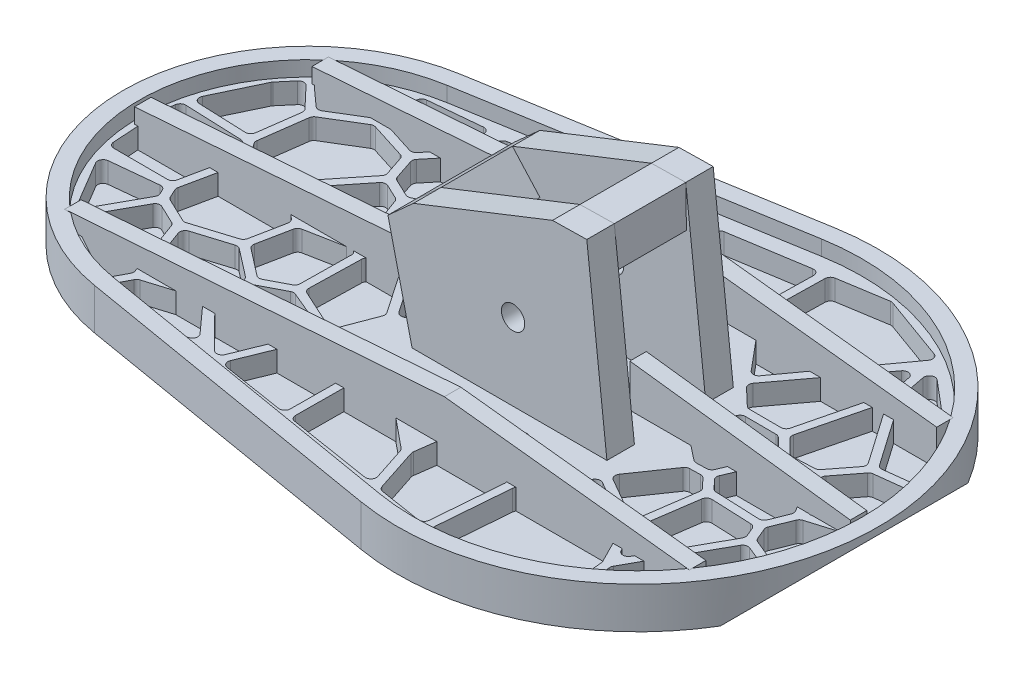
SolidWorks part; units mm, degrees
ref_plane "Front Plane" through (0, 0, 0) normal (0, 0, 1) x (1, 0, 0)
ref_plane "Top Plane" through (0, 0, 0) normal (0, 1, 0) x (1, 0, 0)
ref_plane "Right Plane" through (0, 0, 0) normal (1, 0, 0) x (0, 0, -1)
ref_plane "Plane1" through (0, 34.8481, 0) normal (0, 1, 0) x (1, 0, 0)
sketch "Sketch1" plane through (0, 34.8481, 0) normal (0, 1, 0) x (1, 0, 0)
  line L0 (258.2306, -326.3776) -> (304.8973, -318.4895)
  line L1 (304.8973, -387.5105) -> (258.2306, -379.6224)
  arc A0 (304.8973, -318.4895) -> (304.8973, -387.5105) centre (310.7306, -353) cw
  arc A1 (258.2306, -379.6224) -> (258.2306, -326.3776) centre (262.7306, -353) cw
extrude "Boss-Extrude1" add sketch "Sketch1" along normal blind 0.8
sketch "Sketch2" plane through (0, 34.8481, 0) normal (0, 1, 0) x (1, 0, 0)
  line L0 (258.2306, -326.3776) -> (304.8973, -318.4895)
  line L1 (304.8973, -387.5105) -> (258.2306, -379.6224)
  line L2 (258.6306, -328.7441) -> (305.2973, -320.856)
  line L3 (305.2973, -385.144) -> (258.6306, -377.2559)
  arc A0 (304.8973, -318.4895) -> (304.8973, -387.5105) centre (310.7306, -353) cw
  arc A1 (258.2306, -379.6224) -> (258.2306, -326.3776) centre (262.7306, -353) cw
  arc A2 (305.2973, -320.856) -> (305.2973, -385.144) centre (310.7306, -353) cw
  arc A3 (258.6306, -377.2559) -> (258.6306, -328.7441) centre (262.7306, -353) cw
extrude "Boss-Extrude2" add sketch "Sketch2" along normal blind 6
ref_plane "Plane2" through (0, 35.6481, 0) normal (0, 1, 0) x (1, 0, 0)
sketch "Sketch3" plane through (0, 35.6481, 0) normal (0, 1, 0) x (1, 0, 0)
  line L0 (258.6306, -328.7441) -> (305.2973, -320.856)
  line L1 (305.2973, -385.144) -> (258.6306, -377.2559)
  line L2 (326.9221, -349.4806) -> (324.3999, -355.4885)
  line L3 (323.6806, -355.9786) -> (322.2239, -356.0119)
  line L4 (321.7105, -355.8404) -> (318.4603, -353.279)
  line L5 (318.169, -352.5039) -> (319.154, -347.2263)
  line L6 (319.9437, -346.5731) -> (324.411, -346.5915)
  line L7 (324.9738, -346.8262) -> (326.7506, -348.6056)
  line L8 (267.3257, -343.3736) -> (264.8315, -342.1944)
  line L9 (264.4148, -341.7249) -> (263.4553, -338.8559)
  line L10 (263.5965, -338.0935) -> (266.9026, -334.08)
  line L11 (267.7422, -333.8201) -> (274.2523, -335.7012)
  line L12 (274.8115, -336.2974) -> (275.4141, -339.0298)
  line L13 (274.9878, -339.9191) -> (268.0226, -343.3673)
  line L14 (267.2916, -344.9386) -> (269.8707, -351.9537)
  line L15 (269.2711, -353.0153) -> (263.5775, -354.1111)
  line L16 (262.89, -353.9191) -> (259.2405, -350.622)
  line L17 (259.1528, -349.5278) -> (263.8118, -343.719)
  line L18 (264.7778, -343.4963) -> (266.8826, -344.4914)
  line L19 (256.5796, -335.2605) -> (256.1165, -330.7607)
  line L20 (256.8362, -329.8825) -> (264.3667, -329.1629)
  line L21 (265.1892, -329.6715) -> (266.2297, -332.3696)
  line L22 (266.1007, -333.1661) -> (262.7782, -337.1995)
  line L23 (261.9197, -337.4537) -> (257.1344, -335.9414)
  line L24 (247.9634, -358.7536) -> (240.1536, -358.7314)
  line L25 (239.3575, -357.9815) -> (238.8843, -350.4343)
  line L26 (238.8938, -350.2521) -> (239.1497, -348.7241)
  line L27 (239.9705, -348.0569) -> (248.2357, -348.3854)
  line L28 (248.8538, -348.7182) -> (250.0944, -350.4459)
  line L29 (250.2275, -351.077) -> (248.7486, -358.118)
  line L30 (287.7265, -326.0106) -> (292.3367, -325.2734)
  line L31 (293.2529, -325.9365) -> (295.2909, -338.6247)
  line L32 (295.0443, -339.3388) -> (292.2792, -341.8968)
  line L33 (291.5163, -342.0788) -> (287.1039, -340.8187)
  line L34 (286.5242, -340.0175) -> (287.0534, -326.7686)
  line L35 (309.0913, -383.4055) -> (302.9658, -382.4261)
  line L36 (302.3318, -381.8853) -> (300.2607, -375.5649)
  line L37 (300.2281, -375.2094) -> (301.2567, -367.545)
  line L38 (301.666, -366.9493) -> (305.7474, -364.7193)
  line L39 (306.8303, -365.0328) -> (310.7419, -372.0739)
  line L40 (310.8399, -372.5272) -> (310.015, -382.6804)
  line L41 (272.0014, -362.1821) -> (272.1796, -354.6929)
  line L42 (272.7972, -353.933) -> (275.8082, -353.2287)
  line L43 (276.6521, -353.558) -> (280.7556, -359.5957)
  line L44 (280.842, -360.329) -> (279.0666, -365.0128)
  line L45 (277.9853, -365.4565) -> (272.4679, -362.9284)
  line L46 (342.4873, -355.1029) -> (341.1954, -362.3386)
  line L47 (340.0985, -362.9358) -> (336.6345, -361.4832)
  line L48 (336.2068, -361.0563) -> (335.5307, -359.4535)
  line L49 (335.5259, -358.8433) -> (336.696, -355.9426)
  line L50 (337.2079, -355.4757) -> (341.4697, -354.196)
  line L51 (335.0223, -362.126) -> (329.2112, -372.567)
  line L52 (327.7993, -372.541) -> (326.0122, -369.0323)
  line L53 (325.9333, -368.5543) -> (327.1526, -360.151)
  line L54 (327.9783, -359.4666) -> (333.8421, -359.7162)
  line L55 (334.5452, -360.2046) -> (335.0604, -361.426)
  line L56 (284.2728, -339.8004) -> (277.2578, -339.2063)
  line L57 (276.5441, -338.5814) -> (275.9425, -335.8536)
  line L58 (276.0835, -335.2016) -> (282.13, -327.1334)
  line L59 (282.6439, -326.8232) -> (284.8849, -326.4649)
  line L60 (285.8099, -327.3005) -> (285.139, -339.0488)
  line L61 (272.9662, -376.9017) -> (266.8363, -370.7056)
  line L62 (266.622, -369.979) -> (267.4207, -366.1661)
  line L63 (267.8352, -365.6201) -> (271.0749, -363.9385)
  line L64 (271.7518, -363.9103) -> (277.5821, -366.3456)
  line L65 (278.0155, -367.3834) -> (274.2766, -376.6388)
  line L66 (282.5778, -349.9565) -> (286.7369, -352.3566)
  line L67 (287.1153, -353.2349) -> (286.1519, -357.2775)
  line L68 (285.6357, -357.8479) -> (282.4781, -358.9425)
  line L69 (281.5544, -358.6363) -> (277.6859, -352.9443)
  line L70 (277.7237, -351.9939) -> (278.6589, -350.8289)
  line L71 (279.0998, -350.5509) -> (281.9949, -349.8706)
  line L72 (325.7626, -345.3714) -> (328.0364, -336.1786)
  line L73 (329.4695, -335.9134) -> (334.744, -343.486)
  line L74 (334.7203, -344.4327) -> (332.1377, -347.7711)
  line L75 (331.5406, -348.0808) -> (328.4291, -348.2196)
  line L76 (327.8274, -347.9857) -> (325.9731, -346.1288)
  line L77 (284.9327, -379.5427) -> (276.0285, -378.119)
  line L78 (275.4131, -377.0294) -> (279.2483, -367.5355)
  line L79 (280.3055, -367.0999) -> (285.4433, -369.3042)
  line L80 (285.9279, -370.0457) -> (285.859, -378.7591)
  line L81 (316.3467, -321.536) -> (325.7917, -324.96)
  line L82 (326.1668, -326.1816) -> (315.8792, -340.3724)
  line L83 (314.6178, -340.4161) -> (308.3526, -332.9249)
  line L84 (308.1665, -332.3961) -> (308.3421, -323.3809)
  line L85 (309.0156, -322.6066) -> (315.9477, -321.4982)
  line L86 (250.8942, -340.0762) -> (255.8453, -337.0781)
  line L87 (256.5008, -336.9996) -> (261.7797, -338.6679)
  line L88 (262.2974, -339.177) -> (263.2239, -341.9476)
  line L89 (263.0893, -342.7019) -> (257.7792, -349.3224)
  line L90 (257.203, -349.6204) -> (251.6762, -349.9517)
  line L91 (250.9785, -349.6198) -> (249.7546, -347.9154)
  line L92 (249.6117, -347.3416) -> (250.5158, -340.6533)
  line L93 (341.5202, -344.6918) -> (342.6118, -351.8823)
  line L94 (342.051, -352.7686) -> (337.2248, -354.2177)
  line L95 (336.3234, -353.8866) -> (333.2587, -349.158)
  line L96 (333.2973, -348.2334) -> (335.9395, -344.8179)
  line L97 (336.4776, -344.513) -> (340.6346, -344.0175)
  line L98 (269.1508, -344.2366) -> (274.3823, -342.1195)
  line L99 (275.4434, -342.6144) -> (277.6892, -349.5433)
  line L100 (277.552, -350.2908) -> (276.4424, -351.6731)
  line L101 (276.0007, -351.9513) -> (272.3578, -352.8034)
  line L102 (271.4295, -352.3129) -> (268.7047, -345.2667)
  line L103 (333.791, -358.513) -> (327.3323, -358.238)
  line L104 (326.7858, -357.9892) -> (325.6657, -356.8078)
  line L105 (325.5086, -355.9477) -> (328.0492, -349.896)
  line L106 (328.7512, -349.4064) -> (331.441, -349.2865)
  line L107 (332.148, -349.6506) -> (335.492, -354.8103)
  line L108 (335.5626, -355.5447) -> (334.5669, -358.013)
  line L109 (252.044, -351.1318) -> (257.3083, -350.8163)
  line L110 (257.8925, -351.0212) -> (262.0137, -354.7446)
  line L111 (262.262, -355.4944) -> (261.2874, -360.3902)
  line L112 (260.7406, -360.9978) -> (254.8188, -362.8419)
  line L113 (254.236, -362.7999) -> (250.7985, -361.1572)
  line L114 (250.4174, -360.7715) -> (249.841, -359.5262)
  line L115 (249.7841, -359.0257) -> (251.3089, -351.7659)
  line L116 (327.5391, -333.1914) -> (324.6724, -344.7815)
  line L117 (323.8925, -345.3894) -> (319.3368, -345.3706)
  line L118 (318.7889, -345.1504) -> (316.4047, -342.8841)
  line L119 (316.3142, -341.8264) -> (325.5246, -329.4608)
  line L120 (326.9515, -329.7857) -> (327.5478, -332.8463)
  line L121 (255.0492, -375.6033) -> (246.9826, -371.0852)
  line L122 (246.836, -370.9774) -> (246.3939, -370.5596)
  line L123 (246.2543, -369.6647) -> (249.9996, -362.8773)
  line L124 (250.9661, -362.5673) -> (253.7225, -363.8845)
  line L125 (254.0978, -364.2965) -> (257.1772, -372.6692)
  line L126 (257.1373, -373.2696) -> (256.0648, -375.303)
  line L127 (322.4631, -357.2068) -> (323.9947, -357.1717)
  line L128 (324.5936, -357.4211) -> (325.838, -358.7336)
  line L129 (326.0492, -359.3989) -> (324.9788, -366.7755)
  line L130 (323.7864, -367.353) -> (318.2991, -364.1768)
  line L131 (318.0415, -363.03) -> (321.823, -357.5521)
  line L132 (327.752, -379.9617) -> (316.3557, -384.4543)
  line L133 (315.936, -384.5) -> (311.8645, -383.849)
  line L134 (311.1935, -382.9942) -> (312.0398, -372.5771)
  line L135 (312.1799, -372.1859) -> (316.7911, -365.5393)
  line L136 (317.8491, -365.3029) -> (324.6168, -369.2202)
  line L137 (324.9289, -369.5495) -> (327.8036, -375.1933)
  line L138 (327.8867, -375.4764) -> (328.2546, -379.1375)
  line L139 (247.0752, -335.0861) -> (253.4853, -331.0873)
  line L140 (254.697, -331.6293) -> (255.3478, -335.3819)
  line L141 (254.974, -336.2029) -> (250.5892, -338.858)
  line L142 (249.6397, -338.7683) -> (246.9635, -336.3595)
  line L143 (240.0559, -345.7436) -> (243.2756, -338.9793)
  line L144 (243.3875, -338.8061) -> (245.036, -336.8596)
  line L145 (246.2269, -336.8261) -> (249.1101, -339.8655)
  line L146 (249.3225, -340.5232) -> (248.5185, -346.4707)
  line L147 (247.6939, -347.1629) -> (240.7465, -346.8868)
  line L148 (295.1016, -324.8313) -> (306.2063, -323.0557)
  line L149 (307.1325, -323.8613) -> (306.9639, -332.5185)
  line L150 (306.8473, -332.9189) -> (302.6921, -339.7437)
  line L151 (301.8148, -340.1038) -> (297.0441, -338.9119)
  line L152 (296.4481, -338.2626) -> (294.4381, -325.7482)
  line L153 (336.7163, -334.3662) -> (340.5167, -341.7354)
  line L154 (339.9004, -342.8965) -> (336.5872, -343.2914)
  line L155 (335.8361, -342.9543) -> (328.857, -332.9347)
  line L156 (328.7283, -332.6304) -> (327.9763, -328.771)
  line L157 (329.2776, -328.0067) -> (336.5213, -334.1216)
  line L158 (269.1722, -377.1908) -> (258.1297, -376.3589)
  line L159 (257.4821, -375.188) -> (258.206, -373.8155)
  line L160 (258.6779, -373.4242) -> (265.2057, -371.4117)
  line L161 (266.0363, -371.6414) -> (269.8272, -375.8582)
  line L162 (258.0512, -371.5692) -> (255.5443, -364.7531)
  line L163 (256.0572, -363.7131) -> (261.1952, -362.1131)
  line L164 (261.9229, -362.2444) -> (265.9095, -365.3314)
  line L165 (266.2027, -366.1279) -> (265.4662, -369.644)
  line L166 (264.9188, -370.2445) -> (259.0377, -372.0575)
  line L167 (262.471, -360.5907) -> (263.4102, -355.8728)
  line L168 (264.0436, -355.2434) -> (269.9504, -354.1066)
  line L169 (270.9015, -354.9038) -> (270.7948, -362.2573)
  line L170 (270.3634, -362.9557) -> (267.4876, -364.4485)
  line L171 (266.6292, -364.371) -> (262.7658, -361.3794)
  line L172 (340.1301, -365.1702) -> (334.2839, -374.6283)
  line L173 (334.1324, -374.8078) -> (330.6104, -377.9129)
  line L174 (329.2853, -377.3928) -> (329.0984, -375.5321)
  line L175 (329.1953, -375.0631) -> (335.8045, -363.1881)
  line L176 (336.7993, -362.8338) -> (339.7454, -364.0063)
  line L177 (274.4558, -334.5108) -> (268.0797, -332.6686)
  line L178 (267.5077, -331.9972) -> (267.2823, -330.1561)
  line L179 (267.9442, -329.2698) -> (278.6499, -327.4768)
  line L180 (279.4222, -328.7456) -> (275.318, -334.222)
  line L181 (284.8387, -342.2135) -> (282.1387, -348.2794)
  line L182 (281.5908, -348.7329) -> (279.6104, -349.1982)
  line L183 (278.6663, -348.6661) -> (276.5375, -342.0982)
  line L184 (277.3029, -341.0515) -> (284.1121, -341.0882)
  line L185 (299.8563, -381.9289) -> (287.7292, -379.9899)
  line L186 (287.0556, -379.1936) -> (287.1283, -370.0037)
  line L187 (287.5975, -369.2816) -> (289.4041, -368.4613)
  line L188 (290.2416, -368.5706) -> (298.8944, -375.6526)
  line L189 (299.1479, -376.0226) -> (300.7429, -380.8898)
  line L190 (244.3635, -368.1131) -> (240.6873, -361.9185)
  line L191 (241.294, -360.7144) -> (248.1499, -360.0137)
  line L192 (248.9572, -360.4735) -> (249.2424, -361.0896)
  line L193 (249.2168, -361.8122) -> (245.752, -368.0913)
  arc A0 (305.2973, -320.856) -> (305.2973, -385.144) centre (310.7306, -353) cw
  arc A1 (258.6306, -377.2559) -> (258.6306, -328.7441) centre (262.7306, -353) cw
  arc A2 (326.7506, -348.6056) -> (326.9221, -349.4806) centre (326.1845, -349.1709) cw
  arc A3 (324.3999, -355.4885) -> (323.6806, -355.9786) centre (323.6623, -355.1788) cw
  arc A4 (322.2239, -356.0119) -> (321.7105, -355.8404) centre (322.2057, -355.2121) cw
  arc A5 (318.4603, -353.279) -> (318.169, -352.5039) centre (318.9554, -352.6506) cw
  arc A6 (319.154, -347.2263) -> (319.9437, -346.5731) centre (319.9404, -347.3731) cw
  arc A7 (324.411, -346.5915) -> (324.9738, -346.8262) centre (324.4077, -347.3915) cw
  arc A8 (268.0226, -343.3673) -> (267.3257, -343.3736) centre (267.6677, -342.6503) cw
  arc A9 (264.8315, -342.1944) -> (264.4148, -341.7249) centre (265.1735, -341.4711) cw
  arc A10 (263.4553, -338.8559) -> (263.5965, -338.0935) centre (264.214, -338.6021) cw
  arc A11 (266.9026, -334.08) -> (267.7422, -333.8201) centre (267.5201, -334.5887) cw
  arc A12 (274.2523, -335.7012) -> (274.8115, -336.2974) centre (274.0303, -336.4697) cw
  arc A13 (275.4141, -339.0298) -> (274.9878, -339.9191) centre (274.6329, -339.2021) cw
  arc A14 (266.8826, -344.4914) -> (267.2916, -344.9386) centre (266.5407, -345.2147) cw
  arc A15 (269.8707, -351.9537) -> (269.2711, -353.0153) centre (269.1199, -352.2297) cw
  arc A16 (263.5775, -354.1111) -> (262.89, -353.9191) centre (263.4263, -353.3255) cw
  arc A17 (259.2405, -350.622) -> (259.1528, -349.5278) centre (259.7769, -350.0284) cw
  arc A18 (263.8118, -343.719) -> (264.7778, -343.4963) centre (264.4359, -344.2196) cw
  arc A19 (257.1344, -335.9414) -> (256.5796, -335.2605) centre (257.3754, -335.1786) cw
  arc A20 (256.1165, -330.7607) -> (256.8362, -329.8825) centre (256.9122, -330.6788) cw
  arc A21 (264.3667, -329.1629) -> (265.1892, -329.6715) centre (264.4428, -329.9593) cw
  arc A22 (266.2297, -332.3696) -> (266.1007, -333.1661) centre (265.4832, -332.6575) cw
  arc A23 (262.7782, -337.1995) -> (261.9197, -337.4537) centre (262.1608, -336.6909) cw
  arc A24 (248.7486, -358.118) -> (247.9634, -358.7536) centre (247.9656, -357.9536) cw
  arc A25 (240.1536, -358.7314) -> (239.3575, -357.9815) centre (240.1559, -357.9314) cw
  arc A26 (238.8843, -350.4343) -> (238.8938, -350.2521) centre (239.6828, -350.3843) cw
  arc A27 (239.1497, -348.7241) -> (239.9705, -348.0569) centre (239.9387, -348.8562) cw
  arc A28 (248.2357, -348.3854) -> (248.8538, -348.7182) centre (248.2039, -349.1848) cw
  arc A29 (250.0944, -350.4459) -> (250.2275, -351.077) centre (249.4445, -350.9125) cw
  arc A30 (287.0534, -326.7686) -> (287.7265, -326.0106) centre (287.8528, -326.8005) cw
  arc A31 (292.3367, -325.2734) -> (293.2529, -325.9365) centre (292.463, -326.0634) cw
  arc A32 (295.2909, -338.6247) -> (295.0443, -339.3388) centre (294.501, -338.7516) cw
  arc A33 (292.2792, -341.8968) -> (291.5163, -342.0788) centre (291.736, -341.3095) cw
  arc A34 (287.1039, -340.8187) -> (286.5242, -340.0175) centre (287.3236, -340.0494) cw
  arc A35 (310.015, -382.6804) -> (309.0913, -383.4055) centre (309.2176, -382.6156) cw
  arc A36 (302.9658, -382.4261) -> (302.3318, -381.8853) centre (303.0921, -381.6361) cw
  arc A37 (300.2607, -375.5649) -> (300.2281, -375.2094) centre (301.021, -375.3158) cw
  arc A38 (301.2567, -367.545) -> (301.666, -366.9493) centre (302.0496, -367.6514) cw
  arc A39 (305.7474, -364.7193) -> (306.8303, -365.0328) centre (306.131, -365.4213) cw
  arc A40 (310.7419, -372.0739) -> (310.8399, -372.5272) centre (310.0425, -372.4624) cw
  arc A41 (272.4679, -362.9284) -> (272.0014, -362.1821) centre (272.8012, -362.2011) cw
  arc A42 (272.1796, -354.6929) -> (272.7972, -353.933) centre (272.9794, -354.7119) cw
  arc A43 (275.8082, -353.2287) -> (276.6521, -353.558) centre (275.9904, -354.0077) cw
  arc A44 (280.7556, -359.5957) -> (280.842, -360.329) centre (280.0939, -360.0454) cw
  arc A45 (279.0666, -365.0128) -> (277.9853, -365.4565) centre (278.3186, -364.7292) cw
  arc A46 (341.4697, -354.196) -> (342.4873, -355.1029) centre (341.6998, -354.9623) cw
  arc A47 (341.1954, -362.3386) -> (340.0985, -362.9358) centre (340.4079, -362.198) cw
  arc A48 (336.6345, -361.4832) -> (336.2068, -361.0563) centre (336.9439, -360.7454) cw
  arc A49 (335.5307, -359.4535) -> (335.5259, -358.8433) centre (336.2679, -359.1426) cw
  arc A50 (336.696, -355.9426) -> (337.2079, -355.4757) centre (337.4379, -356.2419) cw
  arc A51 (335.0604, -361.426) -> (335.0223, -362.126) centre (334.3233, -361.737) cw
  arc A52 (329.2112, -372.567) -> (327.7993, -372.541) centre (328.5122, -372.1779) cw
  arc A53 (326.0122, -369.0323) -> (325.9333, -368.5543) centre (326.725, -368.6692) cw
  arc A54 (327.1526, -360.151) -> (327.9783, -359.4666) centre (327.9443, -360.2659) cw
  arc A55 (333.8421, -359.7162) -> (334.5452, -360.2046) centre (333.8081, -360.5155) cw
  arc A56 (285.139, -339.0488) -> (284.2728, -339.8004) centre (284.3403, -339.0032) cw
  arc A57 (277.2578, -339.2063) -> (276.5441, -338.5814) centre (277.3253, -338.4091) cw
  arc A58 (275.9425, -335.8536) -> (276.0835, -335.2016) centre (276.7237, -335.6813) cw
  arc A59 (282.13, -327.1334) -> (282.6439, -326.8232) centre (282.7702, -327.6132) cw
  arc A60 (284.8849, -326.4649) -> (285.8099, -327.3005) centre (285.0112, -327.2549) cw
  arc A61 (274.2766, -376.6388) -> (272.9662, -376.9017) centre (273.5349, -376.3391) cw
  arc A62 (266.8363, -370.7056) -> (266.622, -369.979) centre (267.405, -370.143) cw
  arc A63 (267.4207, -366.1661) -> (267.8352, -365.6201) centre (268.2037, -366.3302) cw
  arc A64 (271.0749, -363.9385) -> (271.7518, -363.9103) centre (271.4435, -364.6485) cw
  arc A65 (277.5821, -366.3456) -> (278.0155, -367.3834) centre (277.2738, -367.0838) cw
  arc A66 (281.9949, -349.8706) -> (282.5778, -349.9565) centre (282.1779, -350.6494) cw
  arc A67 (286.7369, -352.3566) -> (287.1153, -353.2349) centre (286.3371, -353.0495) cw
  arc A68 (286.1519, -357.2775) -> (285.6357, -357.8479) centre (285.3737, -357.092) cw
  arc A69 (282.4781, -358.9425) -> (281.5544, -358.6363) centre (282.2161, -358.1866) cw
  arc A70 (277.6859, -352.9443) -> (277.7237, -351.9939) centre (278.3476, -352.4947) cw
  arc A71 (278.6589, -350.8289) -> (279.0998, -350.5509) centre (279.2828, -351.3297) cw
  arc A72 (325.9731, -346.1288) -> (325.7626, -345.3714) centre (326.5392, -345.5635) cw
  arc A73 (328.0364, -336.1786) -> (329.4695, -335.9134) centre (328.813, -336.3707) cw
  arc A74 (334.744, -343.486) -> (334.7203, -344.4327) centre (334.0876, -343.9432) cw
  arc A75 (332.1377, -347.7711) -> (331.5406, -348.0808) centre (331.505, -347.2816) cw
  arc A76 (328.4291, -348.2196) -> (327.8274, -347.9857) centre (328.3935, -347.4204) cw
  arc A77 (285.859, -378.7591) -> (284.9327, -379.5427) centre (285.059, -378.7528) cw
  arc A78 (276.0285, -378.119) -> (275.4131, -377.0294) centre (276.1548, -377.329) cw
  arc A79 (279.2483, -367.5355) -> (280.3055, -367.0999) centre (279.9901, -367.8351) cw
  arc A80 (285.4433, -369.3042) -> (285.9279, -370.0457) centre (285.1279, -370.0394) cw
  arc A81 (315.9477, -321.4982) -> (316.3467, -321.536) centre (316.0741, -322.2881) cw
  arc A82 (325.7917, -324.96) -> (326.1668, -326.1816) centre (325.5191, -325.7121) cw
  arc A83 (315.8792, -340.3724) -> (314.6178, -340.4161) centre (315.2315, -339.9028) cw
  arc A84 (308.3526, -332.9249) -> (308.1665, -332.3961) centre (308.9663, -332.4117) cw
  arc A85 (308.3421, -323.3809) -> (309.0156, -322.6066) centre (309.1419, -323.3965) cw
  arc A86 (250.5158, -340.6533) -> (250.8942, -340.0762) centre (251.3086, -340.7605) cw
  arc A87 (255.8453, -337.0781) -> (256.5008, -336.9996) centre (256.2597, -337.7625) cw
  arc A88 (261.7797, -338.6679) -> (262.2974, -339.177) centre (261.5387, -339.4308) cw
  arc A89 (263.2239, -341.9476) -> (263.0893, -342.7019) centre (262.4652, -342.2013) cw
  arc A90 (257.7792, -349.3224) -> (257.203, -349.6204) centre (257.1552, -348.8219) cw
  arc A91 (251.6762, -349.9517) -> (250.9785, -349.6198) centre (251.6283, -349.1531) cw
  arc A92 (249.7546, -347.9154) -> (249.6117, -347.3416) centre (250.4045, -347.4488) cw
  arc A93 (340.6346, -344.0175) -> (341.5202, -344.6918) centre (340.7293, -344.8119) cw
  arc A94 (342.6118, -351.8823) -> (342.051, -352.7686) centre (341.8209, -352.0024) cw
  arc A95 (337.2248, -354.2177) -> (336.3234, -353.8866) centre (336.9947, -353.4515) cw
  arc A96 (333.2587, -349.158) -> (333.2973, -348.2334) centre (333.9301, -348.7229) cw
  arc A97 (335.9395, -344.8179) -> (336.4776, -344.513) centre (336.5723, -345.3074) cw
  arc A98 (268.7047, -345.2667) -> (269.1508, -344.2366) centre (269.4509, -344.9782) cw
  arc A99 (274.3823, -342.1195) -> (275.4434, -342.6144) centre (274.6824, -342.861) cw
  arc A100 (277.6892, -349.5433) -> (277.552, -350.2908) centre (276.9282, -349.79) cw
  arc A101 (276.4424, -351.6731) -> (276.0007, -351.9513) centre (275.8185, -351.1723) cw
  arc A102 (272.3578, -352.8034) -> (271.4295, -352.3129) centre (272.1756, -352.0244) cw
  arc A103 (334.5669, -358.013) -> (333.791, -358.513) centre (333.825, -357.7137) cw
  arc A104 (327.3323, -358.238) -> (326.7858, -357.9892) centre (327.3663, -357.4388) cw
  arc A105 (325.6657, -356.8078) -> (325.5086, -355.9477) centre (326.2462, -356.2574) cw
  arc A106 (328.0492, -349.896) -> (328.7512, -349.4064) centre (328.7868, -350.2056) cw
  arc A107 (331.441, -349.2865) -> (332.148, -349.6506) centre (331.4767, -350.0857) cw
  arc A108 (335.492, -354.8103) -> (335.5626, -355.5447) centre (334.8207, -355.2454) cw
  arc A109 (251.3089, -351.7659) -> (252.044, -351.1318) centre (252.0918, -351.9304) cw
  arc A110 (257.3083, -350.8163) -> (257.8925, -351.0212) centre (257.3561, -351.6148) cw
  arc A111 (262.0137, -354.7446) -> (262.262, -355.4944) centre (261.4774, -355.3382) cw
  arc A112 (261.2874, -360.3902) -> (260.7406, -360.9978) centre (260.5028, -360.234) cw
  arc A113 (254.8188, -362.8419) -> (254.236, -362.7999) centre (254.5809, -362.0781) cw
  arc A114 (250.7985, -361.1572) -> (250.4174, -360.7715) centre (251.1434, -360.4354) cw
  arc A115 (249.841, -359.5262) -> (249.7841, -359.0257) centre (250.567, -359.1901) cw
  arc A116 (327.5478, -332.8463) -> (327.5391, -333.1914) centre (326.7625, -332.9993) cw
  arc A117 (324.6724, -344.7815) -> (323.8925, -345.3894) centre (323.8958, -344.5894) cw
  arc A118 (319.3368, -345.3706) -> (318.7889, -345.1504) centre (319.3401, -344.5706) cw
  arc A119 (316.4047, -342.8841) -> (316.3142, -341.8264) centre (316.9558, -342.3042) cw
  arc A120 (325.5246, -329.4608) -> (326.9515, -329.7857) centre (326.1662, -329.9387) cw
  arc A121 (256.0648, -375.303) -> (255.0492, -375.6033) centre (255.4106, -374.958) cw
  arc A122 (246.9826, -371.0852) -> (246.836, -370.9774) centre (247.344, -370.4399) cw
  arc A123 (246.3939, -370.5596) -> (246.2543, -369.6647) centre (246.9019, -370.022) cw
  arc A124 (249.9996, -362.8773) -> (250.9661, -362.5673) centre (250.6472, -363.2346) cw
  arc A125 (253.7225, -363.8845) -> (254.0978, -364.2965) centre (253.4036, -364.5518) cw
  arc A126 (257.1772, -372.6692) -> (257.1373, -373.2696) centre (256.4831, -372.9245) cw
  arc A127 (321.823, -357.5521) -> (322.4631, -357.2068) centre (322.4814, -358.0065) cw
  arc A128 (323.9947, -357.1717) -> (324.5936, -357.4211) centre (324.013, -357.9715) cw
  arc A129 (325.838, -358.7336) -> (326.0492, -359.3989) centre (325.2574, -359.2841) cw
  arc A130 (324.9788, -366.7755) -> (323.7864, -367.353) centre (324.1871, -366.6606) cw
  arc A131 (318.2991, -364.1768) -> (318.0415, -363.03) centre (318.6999, -363.4845) cw
  arc A132 (328.2546, -379.1375) -> (327.752, -379.9617) centre (327.4586, -379.2175) cw
  arc A133 (316.3557, -384.4543) -> (315.936, -384.5) centre (316.0623, -383.71) cw
  arc A134 (311.8645, -383.849) -> (311.1935, -382.9942) centre (311.9908, -383.059) cw
  arc A135 (312.0398, -372.5771) -> (312.1799, -372.1859) centre (312.8372, -372.6419) cw
  arc A136 (316.7911, -365.5393) -> (317.8491, -365.3029) centre (317.4484, -365.9953) cw
  arc A137 (324.6168, -369.2202) -> (324.9289, -369.5495) centre (324.216, -369.9126) cw
  arc A138 (327.8036, -375.1933) -> (327.8867, -375.4764) centre (327.0907, -375.5564) cw
  arc A139 (246.9635, -336.3595) -> (247.0752, -335.0861) centre (247.4987, -335.7649) cw
  arc A140 (253.4853, -331.0873) -> (254.697, -331.6293) centre (253.9087, -331.766) cw
  arc A141 (255.3478, -335.3819) -> (254.974, -336.2029) centre (254.5596, -335.5186) cw
  arc A142 (250.5892, -338.858) -> (249.6397, -338.7683) centre (250.1749, -338.1737) cw
  arc A143 (240.7465, -346.8868) -> (240.0559, -345.7436) centre (240.7783, -346.0874) cw
  arc A144 (243.2756, -338.9793) -> (243.3875, -338.8061) centre (243.998, -339.3232) cw
  arc A145 (245.036, -336.8596) -> (246.2269, -336.8261) centre (245.6465, -337.3766) cw
  arc A146 (249.1101, -339.8655) -> (249.3225, -340.5232) centre (248.5297, -340.416) cw
  arc A147 (248.5185, -346.4707) -> (247.6939, -347.1629) centre (247.7257, -346.3636) cw
  arc A148 (294.4381, -325.7482) -> (295.1016, -324.8313) centre (295.2279, -325.6213) cw
  arc A149 (306.2063, -323.0557) -> (307.1325, -323.8613) centre (306.3327, -323.8457) cw
  arc A150 (306.9639, -332.5185) -> (306.8473, -332.9189) centre (306.164, -332.5029) cw
  arc A151 (302.6921, -339.7437) -> (301.8148, -340.1038) centre (302.0088, -339.3277) cw
  arc A152 (297.0441, -338.9119) -> (296.4481, -338.2626) centre (297.238, -338.1357) cw
  arc A153 (336.5213, -334.1216) -> (336.7163, -334.3662) centre (336.0053, -334.7329) cw
  arc A154 (340.5167, -341.7354) -> (339.9004, -342.8965) centre (339.8057, -342.1021) cw
  arc A155 (336.5872, -343.2914) -> (335.8361, -342.9543) centre (336.4926, -342.497) cw
  arc A156 (328.857, -332.9347) -> (328.7283, -332.6304) centre (329.5135, -332.4774) cw
  arc A157 (327.9763, -328.771) -> (329.2776, -328.0067) centre (328.7616, -328.618) cw
  arc A158 (269.8272, -375.8582) -> (269.1722, -377.1908) centre (269.2323, -376.393) cw
  arc A159 (258.1297, -376.3589) -> (257.4821, -375.188) centre (258.1898, -375.5612) cw
  arc A160 (258.206, -373.8155) -> (258.6779, -373.4242) centre (258.9136, -374.1887) cw
  arc A161 (265.2057, -371.4117) -> (266.0363, -371.6414) centre (265.4414, -372.1762) cw
  arc A162 (259.0377, -372.0575) -> (258.0512, -371.5692) centre (258.802, -371.293) cw
  arc A163 (255.5443, -364.7531) -> (256.0572, -363.7131) centre (256.2951, -364.4769) cw
  arc A164 (261.1952, -362.1131) -> (261.9229, -362.2444) centre (261.4331, -362.8769) cw
  arc A165 (265.9095, -365.3314) -> (266.2027, -366.1279) centre (265.4197, -365.9639) cw
  arc A166 (265.4662, -369.644) -> (264.9188, -370.2445) centre (264.6832, -369.48) cw
  arc A167 (262.7658, -361.3794) -> (262.471, -360.5907) centre (263.2556, -360.7469) cw
  arc A168 (263.4102, -355.8728) -> (264.0436, -355.2434) centre (264.1948, -356.029) cw
  arc A169 (269.9504, -354.1066) -> (270.9015, -354.9038) centre (270.1016, -354.8922) cw
  arc A170 (270.7948, -362.2573) -> (270.3634, -362.9557) centre (269.9949, -362.2457) cw
  arc A171 (267.4876, -364.4485) -> (266.6292, -364.371) centre (267.119, -363.7385) cw
  arc A172 (339.7454, -364.0063) -> (340.1301, -365.1702) centre (339.4496, -364.7496) cw
  arc A173 (334.2839, -374.6283) -> (334.1324, -374.8078) centre (333.6034, -374.2077) cw
  arc A174 (330.6104, -377.9129) -> (329.2853, -377.3928) centre (330.0813, -377.3128) cw
  arc A175 (329.0984, -375.5321) -> (329.1953, -375.0631) centre (329.8944, -375.4521) cw
  arc A176 (335.8045, -363.1881) -> (336.7993, -362.8338) centre (336.5035, -363.5772) cw
  arc A177 (275.318, -334.222) -> (274.4558, -334.5108) centre (274.6778, -333.7423) cw
  arc A178 (268.0797, -332.6686) -> (267.5077, -331.9972) centre (268.3018, -331.9) cw
  arc A179 (267.2823, -330.1561) -> (267.9442, -329.2698) centre (268.0764, -330.0588) cw
  arc A180 (278.6499, -327.4768) -> (279.4222, -328.7456) centre (278.7821, -328.2658) cw
  arc A181 (284.1121, -341.0882) -> (284.8387, -342.2135) centre (284.1078, -341.8882) cw
  arc A182 (282.1387, -348.2794) -> (281.5908, -348.7329) centre (281.4078, -347.9541) cw
  arc A183 (279.6104, -349.1982) -> (278.6663, -348.6661) centre (279.4274, -348.4195) cw
  arc A184 (276.5375, -342.0982) -> (277.3029, -341.0515) centre (277.2986, -341.8515) cw
  arc A185 (300.7429, -380.8898) -> (299.8563, -381.9289) centre (299.9826, -381.139) cw
  arc A186 (287.7292, -379.9899) -> (287.0556, -379.1936) centre (287.8555, -379.1999) cw
  arc A187 (287.1283, -370.0037) -> (287.5975, -369.2816) centre (287.9282, -370.01) cw
  arc A188 (289.4041, -368.4613) -> (290.2416, -368.5706) centre (289.7349, -369.1897) cw
  arc A189 (298.8944, -375.6526) -> (299.1479, -376.0226) centre (298.3877, -376.2717) cw
  arc A190 (245.752, -368.0913) -> (244.3635, -368.1131) centre (245.0515, -367.7048) cw
  arc A191 (240.6873, -361.9185) -> (241.294, -360.7144) centre (241.3753, -361.5102) cw
  arc A192 (248.1499, -360.0137) -> (248.9572, -360.4735) centre (248.2312, -360.8096) cw
  arc A193 (249.2424, -361.0896) -> (249.2168, -361.8122) centre (248.5164, -361.4257) cw
extrude "Boss-Extrude3" add sketch "Sketch3" along normal blind 3
ref_plane "Plane3" through (0, 0, 333.8) normal (0, 0, 1) x (1, 0, 0)
sketch "Sketch4" plane through (0, 0, 333.8) normal (0, 0, 1) x (1, 0, 0)
  line L0 (246.4642, 35.6481) -> (246.4642, 40.8481)
  line L1 (246.4642, 40.8481) -> (301.7365, 44.8481)
  line L2 (301.7365, 44.8481) -> (337.4106, 40.8481)
  line L3 (337.4106, 40.8481) -> (337.4106, 35.6481)
  line L4 (337.4106, 35.6481) -> (246.4642, 35.6481)
extrude "Boss-Extrude4" add sketch "Sketch4" along normal blind 2.4
ref_plane "Plane4" through (0, 0, 351.8) normal (0, 0, 1) x (1, 0, 0)
sketch "Sketch5" plane through (0, 0, 351.8) normal (0, 0, 1) x (1, 0, 0)
  line L0 (238.6315, 35.6481) -> (238.6315, 40.8481)
  line L1 (238.6315, 40.8481) -> (292.7365, 44.8481)
  line L2 (292.7365, 44.8481) -> (292.7365, 35.6481)
  line L3 (292.7365, 35.6481) -> (238.6315, 35.6481)
extrude "Boss-Extrude5" add sketch "Sketch5" along normal blind 2.4
sketch "Sketch6" plane through (0, 0, 351.8) normal (0, 0, 1) x (1, 0, 0)
  line L0 (310.7365, 35.6481) -> (310.7365, 44.8481)
  line L1 (310.7365, 44.8481) -> (342.8298, 40.8481)
  line L2 (342.8298, 40.8481) -> (342.8298, 35.6481)
  line L3 (342.8298, 35.6481) -> (310.7365, 35.6481)
extrude "Boss-Extrude6" add sketch "Sketch6" along normal blind 2.4
ref_plane "Plane5" through (0, 0, 369.8) normal (0, 0, 1) x (1, 0, 0)
sketch "Sketch7" plane through (0, 0, 369.8) normal (0, 0, 1) x (1, 0, 0)
  line L0 (246.4642, 35.6481) -> (246.4642, 40.8481)
  line L1 (246.4642, 40.8481) -> (301.7365, 44.8481)
  line L2 (301.7365, 44.8481) -> (337.4106, 40.8481)
  line L3 (337.4106, 40.8481) -> (337.4106, 35.6481)
  line L4 (337.4106, 35.6481) -> (246.4642, 35.6481)
extrude "Boss-Extrude7" add sketch "Sketch7" along normal blind 2.4
ref_plane "Plane6" through (0, 0, 313) normal (0, 0, 1) x (1, 0, 0)
sketch "Sketch8" plane through (0, 0, 313) normal (0, 0, 1) x (1, 0, 0)
  line L0 (340.7306, 34.8481) -> (340.7306, 33.8481)
  line L1 (340.7306, 33.8481) -> (346.7306, 33.8481)
  line L2 (346.7306, 33.8481) -> (346.7306, 40.8481)
  line L3 (346.7306, 40.8481) -> (340.7306, 34.8481)
extrude "Cut-Extrude1" cut sketch "Sketch8" along normal blind 80
ref_plane "Plane7" through (0, 0, 343.8) normal (0, 0, 1) x (1, 0, 0)
sketch "Sketch9" plane through (0, 0, 343.8) normal (0, 0, 1) x (1, 0, 0)
  line L0 (283.5249, 53.6348) -> (287.7365, 35.6481)
  line L1 (287.7365, 35.6481) -> (315.7365, 35.6481)
  line L2 (315.7365, 35.6481) -> (312.473, 65.0378)
  line L3 (312.473, 65.0378) -> (307.4738, 64.9505)
  line L4 (307.4738, 64.9505) -> (287.2407, 56.9805)
  line L5 (287.2407, 56.9805) -> (283.5249, 53.6348)
  circle A0 centre (301.7365, 49.8481) radius 1.7
extrude "Boss-Extrude8" add sketch "Sketch9" along normal blind 4
ref_plane "Plane8" through (0, 0, 358.2) normal (0, 0, 1) x (1, 0, 0)
sketch "Sketch10" plane through (0, 0, 358.2) normal (0, 0, 1) x (1, 0, 0)
  line L0 (283.5249, 53.6348) -> (287.7365, 35.6481)
  line L1 (287.7365, 35.6481) -> (315.7365, 35.6481)
  line L2 (315.7365, 35.6481) -> (312.473, 65.0378)
  line L3 (312.473, 65.0378) -> (307.4738, 64.9505)
  line L4 (307.4738, 64.9505) -> (287.2407, 56.9805)
  line L5 (287.2407, 56.9805) -> (283.5249, 53.6348)
  circle A0 centre (301.7365, 49.8481) radius 1.7
extrude "Boss-Extrude9" add sketch "Sketch10" along normal blind 4
ref_plane "Plane9" through (0, 0, 347.8) normal (0, 0, 1) x (1, 0, 0)
sketch "Sketch11" plane through (0, 0, 347.8) normal (0, 0, 1) x (1, 0, 0)
  line L0 (307.5785, 58.9514) -> (312.5777, 59.0387)
  line L1 (312.5777, 59.0387) -> (312.473, 65.0378)
  line L2 (312.473, 65.0378) -> (307.4738, 64.9505)
  line L3 (307.4738, 64.9505) -> (307.5785, 58.9514)
  line L4 (291.2554, 52.5216) -> (287.5397, 49.1759)
  line L5 (287.5397, 49.1759) -> (283.5249, 53.6348)
  line L6 (283.5249, 53.6348) -> (287.2407, 56.9805)
  line L7 (287.2407, 56.9805) -> (291.2554, 52.5216)
extrude "Boss-Extrude10" add sketch "Sketch11" along normal blind 10.4
ref_plane "Plane10" through (301.7365, 0, 0) normal (1, 0, 0) x (0, 0, -1)
ref_plane "Plane11" through (0, 49.8481, 0) normal (0, 1, 0) x (1, 0, 0)
ref_axis "ANKLE_AXIS" through (301.7365, 49.8481, 391.5) along (0, 0, -1)
